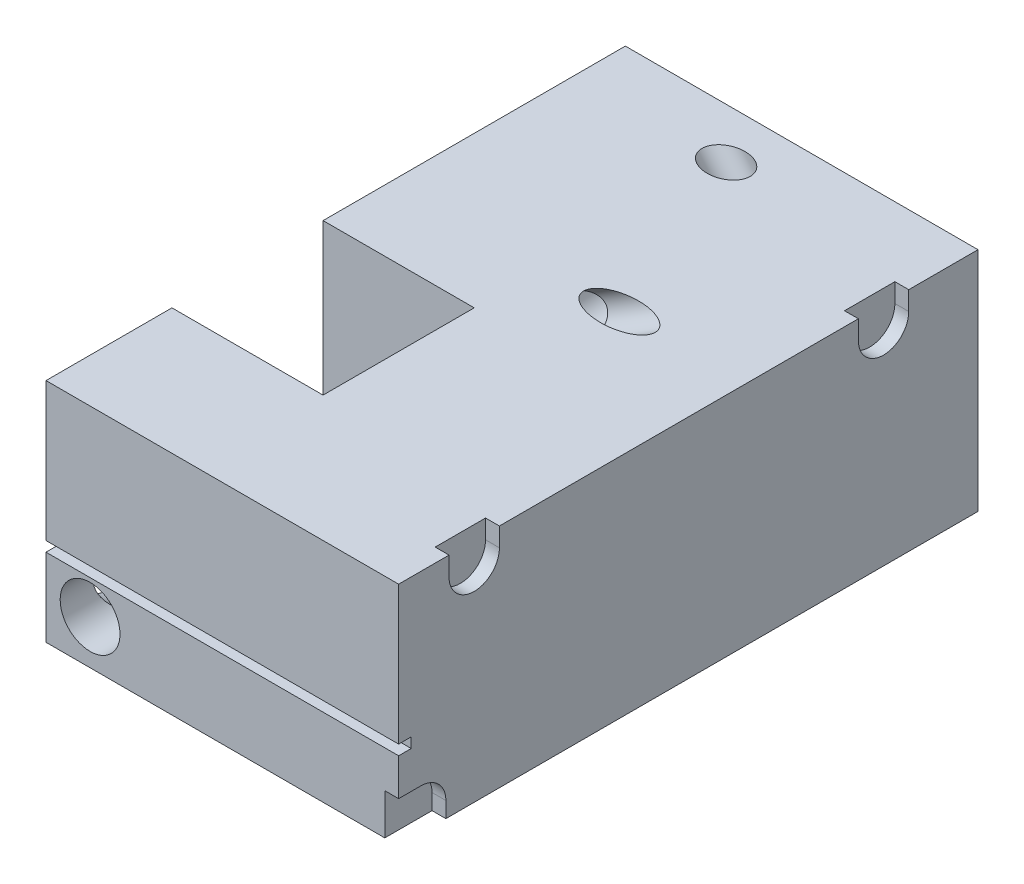
SolidWorks part; units mm, degrees
note: '?' marks a value the reader was unsure of.
material "ПТФЭ (общий)"
ref_plane "Спереди" through (0, 0, 0) normal (0, 0, 1) x (1, 0, 0)
ref_plane "Сверху" through (0, 0, 0) normal (0, 1, 0) x (1, 0, 0)
ref_plane "Справа" through (0, 0, 0) normal (1, 0, 0) x (0, 0, -1)
sketch "Эскиз1" plane through (0, 0, 0) normal (0, 0, 1) x (1, 0, 0)
  line L1 (-56, 0) -> (0, 0)
  line L2 (-56, 0) -> (-56, 36)
  line L3 (-56, 36) -> (0, 36)
  line L4 (0, 0) -> (0, 36)
  dimension "D1" = 36
  dimension "D2" = 56
extrude "Бобышка-Вытянуть1" add sketch "Эскиз1" along normal blind 92
sketch "Эскиз2" plane through (0, 0, 0) normal (0, 0, -1) x (-1, 0, 0)
  line L0 (0, 0) -> (0, 36) construction
  line L1 (56, 0) -> (0, 0) construction
  circle A0 centre (16, 16) radius 14
  dimension "D1" = 28
  dimension "D3" = 16
  dimension "D2" = 16
extrude "Вырез-Вытянуть1" cut sketch "Эскиз2" against normal blind 82
sketch "Эскиз5" plane through (0, 0, 0) normal (0, 0, -1) x (-1, 0, 0)
  circle A0 centre (42.5, 22) radius 12
  circle A1 centre (28, 31) radius 3.5
  circle A2 centre (16, 16) radius 14 construction
  circle A3 centre (16, 16) radius 14 construction
  dimension "D1" = 24
  dimension "D2" = 26.5
  dimension "D3" = 6
  dimension "D4" = 7
  dimension "D5" = 15
  dimension "D6" = 12
extrude "Вырез-Вытянуть2" cut sketch "Эскиз5" against normal blind 40
sketch "Эскиз7" plane through (0, 0, 0) normal (0, -1, 0) x (1, 0, 0)
  line L0 (-56, 48) -> (-32, 48)
  line L1 (-56, 92) -> (-56, 0) construction
  line L2 (-32, 48) -> (-32, 72)
  line L4 (0, 92) -> (0, 0) construction
  line L5 (0, 0) -> (-56, 0) construction
  line L6 (-32, 72) -> (-56, 72)
  dimension "D1" = 32
  dimension "D2" = 48
  dimension "D3" = 24
extrude "Вырез-Вытянуть4" cut sketch "Эскиз7" against normal through all
sketch "Эскиз6" plane through (0, 0, 92) normal (0, 0, -1) x (-1, 0, 0)
  circle A0 centre (49, 7) radius 4.75
  circle A3 centre (42.5, 22) radius 12 construction
  circle A4 centre (42.5, 22) radius 12 construction
  dimension "D1" = 9.5
  dimension "D2" = 15
  dimension "D3" = 6.5
extrude "Вырез-Вытянуть3" cut sketch "Эскиз6" along normal offset from surface (60 mm away) 8 up to face at (-54.5, 22, 40) offset beyond the face yes
ref_axis "Ось1" through (-16, 16, 82) along (0, 0, -1)?
ref_axis "Ось2" through (-42.5, 22, 40) along (0, 0, -1)?
ref_axis "Ось3" through (-28, 31, 40) along (0, 0, -1)?
ref_plane "Плоскость2" through (-1.9512, -1.561, 0) normal (0.7809, 0.6247, 0) x (0, 0, -1)
ref_plane "Плоскость3" through (-21.6773, 34.9245, 0) normal (0.5274, -0.8496, 0) x (0.8496, 0.5274, 0)
ref_plane "Плоскость4" through (-6.3227, -3.9245, 0) normal (-0.8496, -0.5274, 0) x (0, 0, 1)
ref_plane "Плоскость5" through (-26.0488, 32.561, 0) normal (0.6247, -0.7809, 0) x (0.7809, 0.6247, 0)
sketch "Эскиз15" plane through (-6.3227, -3.9245, 0) normal (-0.8496, -0.5274, 0) x (0, 0, 1)
  line L0 (40, 41.105) -> (0, 41.105) construction
  line L2 (0, 60.1194) -> (0, 29.5323) construction
  circle A0 centre (37, 41.105) radius 3
  dimension "D1" = 6
  dimension "D2" = 37
extrude "Вырез-Вытянуть8" cut sketch "Эскиз15" against normal up to surface and the other way up to surface up to face at (-36, 36, 53) other way up to face at (-54.5, 22, 0)
sketch "Эскиз16" plane through (-26.0488, 32.561, 0) normal (0.6247, -0.7809, 0) x (0.7809, 0.6247, 0)
  line L0 (-43.7287, 0) -> (0, 0) construction
  line L1 (-2.4988, 40) -> (-2.4988, 0) construction
  circle A0 centre (-2.4988, 8) radius 3
  dimension "D1" = 6
  dimension "D2" = 8
extrude "Вырез-Вытянуть9" cut sketch "Эскиз16" against normal up to surface and the other way up to surface up to face at (-25.6331, 36, 37) other way up to face at (-30, 16, 82)
sketch "Эскиз17" plane through (-56, 0, 0) normal (-1, 0, 0) x (0, 0, 1)
  line L0 (0, 3.5) -> (9.6162, 0)
  line L1 (0, 36) -> (0, 0) construction
  line L2 (48, 0) -> (0, 0) construction
  line M3 (0, 36) -> (0, 0)
  line M4 (0, 0) -> (48, 0)
  dimension "D1" = 20
  dimension "D2" = 3.5
extrude "скос" [suppressed] cut sketch "Эскиз17" against normal blind 18 contours L0 M3 M4
hole_wizard "1/4  NPT" [suppressed] positions "Эскиз12" profile "Эскиз11" size "1/4" standard "Ansi (в дюймах)"
sketch "Эскиз12" [suppressed] plane through (2.9531, 3.009, 1.349) normal (0, -0.9397, -0.342) x (1, 0, 0)
  line L3 (-40.9531, -1.4356) -> (-58.9531, -1.4356) construction
  line L4 (-58.9531, -1.4356) -> (-58.9531, 8.7978) construction
  point P0 (-49.9531, 7.5644)
  dimension "D1" = 9
  dimension "D2" = 9
sketch "Эскиз11" plane through (-47, 0.4218, 8.4572) normal (1, 0, 0) x (0, 0.342, -0.9397)
  line L0 (0, 0) -> (0, 11.1248)
  line L1 (0, 11.1248) -> (5.5626, 11.1248)
  line L3 (5.5626, 11.1248) -> (5.5626, 10.02)
  line L4 (5.5626, 10.02) -> (6.5713, 10.02)
  line L5 (6.5713, 10.02) -> (6.858, 0.4446)
  line L6 (6.858, 0.4446) -> (7.493, 0)
  line L7 (7.493, 0) -> (0, 0)
  line L8 (0, -6.35) -> (0, 107.95) construction
  line L9 (-6.858, 0.4446) -> (-7.493, 0) construction
  line L11 (-5.5626, 10.02) -> (-6.5713, 10.02) construction
  line L12 (-6.5713, 10.02) -> (-6.858, 0.4446) construction
  dimension "Диаметр проходного сверла" = 11.1252
  dimension "Глубина проходного сверла" = 11.1248
  dimension "Диаметр резьбы" = 13.716
  dimension "Угол резьбы" = 3.43
  dimension "Глубина резьбы" = 10.02
  dimension "Диаметр передней зенковки" = 14.986
  dimension "Угол передней зенковки" = 110
sketch "Эскиз18" plane through (0, 36, 0) normal (0, 1, 0) x (1, 0, 0)
  line L0 (-58.3415, -11) -> (-56, -11) construction
  line L2 (-58.3415, -8) -> (-56, -8)
  line L3 (-58.3415, -14) -> (-56, -14)
  line L4 (0, 0) -> (-56, 0) construction
  line L5 (-53, -11) -> (-53, 0) construction
  line L6 (-56, -48) -> (-56, 0) construction
  arc A0 (-58.3415, -8) -> (-58.3415, -14) centre (-58.3415, -11) ccw
  arc A1 (-56, -14) -> (-56, -8) centre (-56, -11) ccw
  point P4 (-57.1707, -11)
  line M8 (-56, 0) -> (-56, -48)
  dimension "D1" = 6
  dimension "D2" = 11
  dimension "D3" = 3
extrude "Вырез-Вытянуть11" [suppressed] cut sketch "Эскиз18" against normal blind 4 contours L3 A1 L2 M8
sketch "Эскиз19" plane through (0, 0, 0) normal (1, 0, 0) x (0, 0, -1)
  line L0 (-92, 23) -> (-77, 23)
  line L1 (-92, 0) -> (-92, 36) construction
  line L2 (-74, 20) -> (-74, 0)
  line L3 (-92, 0) -> (0, 0) construction
  arc A0 (-74, 20) -> (-77, 23) centre (-77, 20) ccw
  line M3 (-92, 36) -> (-92, 0)
  line M4 (-92, 0) -> (0, 0)
  dimension "D3" = 3
  dimension "D1" = 23
  dimension "D2" = 18
extrude "Вырез-Вытянуть12" [suppressed] cut sketch "Эскиз19" against normal blind 2.5 contours L2 A0 L0 M3 M4
sketch "Эскиз20" plane through (-56, 0, 0) normal (-1, 0, 0) x (0, 0, 1)
  line L1 (72, 0) -> (72, 36) construction
  line L2 (92, 0) -> (72, 0) construction
  circle A0 centre (82, 7) radius 4.75
  dimension "D2" = 7
  dimension "D3" = 9.5
  dimension "D1" = 10
extrude "Вырез-Вытянуть13" cut sketch "Эскиз20" against normal blind 38
sketch "Эскиз21" plane through (0, 0, 0) normal (0, -1, 0) x (1, 0, 0)
  line L0 (-56, 0) -> (0, 0) construction
  line L1 (-56, 48) -> (-56, 0) construction
  circle A0 centre (-47, 16) radius 3
  dimension "D1" = 6
  dimension "D2" = 16
  dimension "D3" = 9
extrude "Вырез-Вытянуть14" cut sketch "Эскиз21" against normal up to next
sketch "Эскиз22" plane through (0, 0, 0) normal (1, 0, 0) x (0, 0, -1)
  line L0 (-84.5, 0) -> (-84.5, 2.5)
  line L1 (-92, 0) -> (0, 0) construction
  line L2 (-92, 6.5) -> (-88.5, 6.5)
  line L3 (-92, 0) -> (-92, 36) construction
  line L4 (-84, 36) -> (-84, 33)
  line L5 (-92, 36) -> (0, 36) construction
  line L6 (-76, 36) -> (-76, 33)
  line L7 (-19, 36) -> (-19, 33)
  line L8 (-11, 36) -> (-11, 33)
  line L9 (-80, 29) -> (-15, 29) construction
  line L10 (0, 0) -> (0, 36) construction
  arc A0 (-88.5, 6.5) -> (-84.5, 2.5) centre (-88.5, 2.5) cw
  arc A1 (-84, 33) -> (-76, 33) centre (-80, 33) ccw
  arc A2 (-19, 33) -> (-11, 33) centre (-15, 33) ccw
  line M2 (0, 36) -> (-92, 36)
  line M3 (-92, 36) -> (-92, 0)
  line M4 (-92, 0) -> (0, 0)
  dimension "D1" = 4
  dimension "D7" = 65
  dimension "D2" = 7.5
  dimension "D3" = 6.5
  dimension "D4" = 8
  dimension "D5" = 7
  dimension "D6" = 15
extrude "Вырез-Вытянуть15" cut sketch "Эскиз22" against normal blind 2.2 contours A0 L2 L0 M3 M4 | L4 A1 L6 M2 | L7 A2 L8 M2
sketch "Эскиз23" plane through (0, 0, 0) normal (1, 0, 0) x (0, 0, -1)
  line L0 (-92, 12.4) -> (-90, 12.4)
  line L2 (-90, 12.4) -> (-90, 14)
  line L3 (-90, 14) -> (-92, 14)
  line L6 (-92, 6.5) -> (-92, 36) construction
  line L7 (-92, 36) -> (-84, 36) construction
  line M29 (-92, 36) -> (-92, 6.5)
  dimension "D1" = 1.6
  dimension "D2" = 22
  dimension "D3" = 2
extrude "Вырез-Вытянуть16" cut sketch "Эскиз23" against normal through all contours L2 L3 L0 M29
